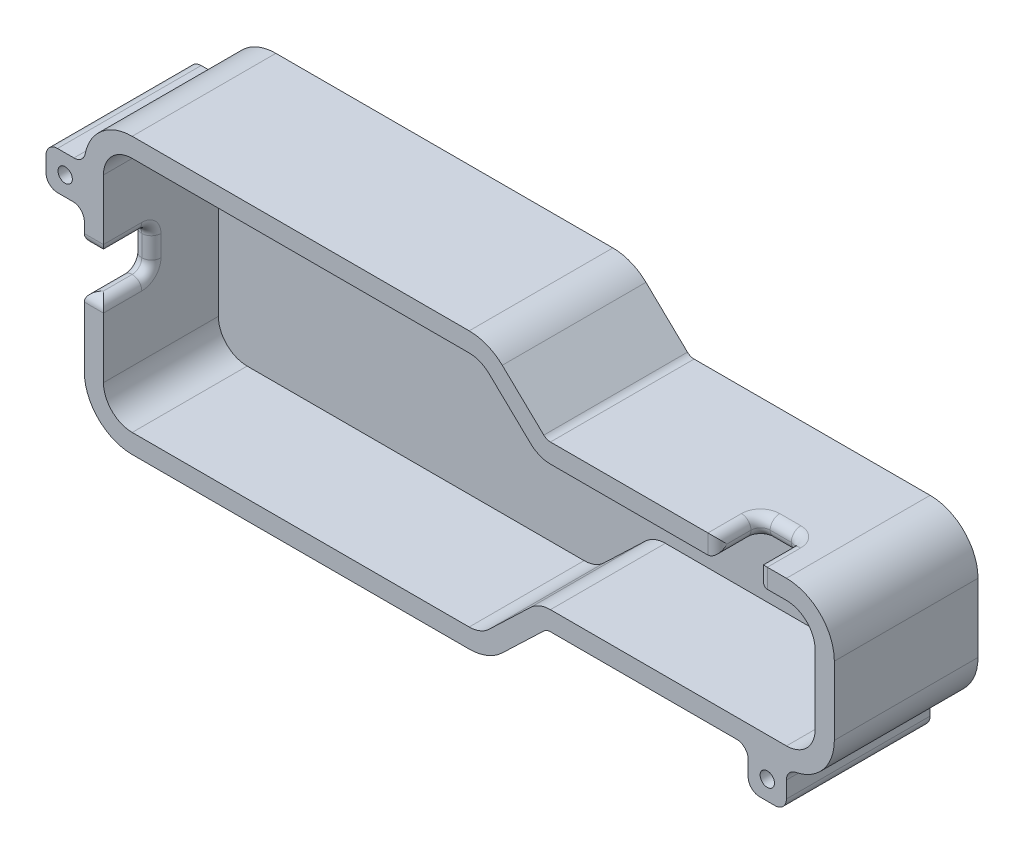
SolidWorks part; units mm, degrees
ref_plane "Front Plane" through (0, 0, 0) normal (0, 0, 1) x (1, 0, 0)
ref_plane "Top Plane" through (0, 0, 0) normal (0, 1, 0) x (1, 0, 0)
ref_plane "Right Plane" through (0, 0, 0) normal (1, 0, 0) x (0, 0, -1)
sketch "Sketch2" plane through (0, 0, 0) normal (0, 0, 1) x (1, 0, 0)
  line L0 (-34.29, 10.16) -> (0, 10.16)
  line L1 (-34.29, 10.16) -> (-34.29, 0)
  line L2 (-34.29, 0) -> (0, 0)
  line L3 (0, 10.16) -> (0, 0)
  line L4 (-69.31, 13.97) -> (-36.29, 13.97)
  line L5 (-69.31, 13.97) -> (-69.31, -3.81)
  line L6 (-69.31, -3.81) -> (-36.29, -3.81)
  line L7 (-36.29, 13.97) -> (-36.29, -3.81)
  line L8 (-31.29, 10.16) -> (-31.29, 0)
  line L9 (-71.31, 15.97) -> (-34.29, 15.97)
  line L10 (-34.29, 15.97) -> (-34.29, 12.16)
  line L11 (-34.29, 12.16) -> (-31.29, 12.16)
  line L12 (-31.29, 12.16) -> (-31.29, -2)
  line L13 (-31.29, -2) -> (-34.29, -2)
  line L14 (-34.29, -2) -> (-34.29, -5.81)
  line L15 (-34.29, -5.81) -> (-71.31, -5.81)
  line L16 (-71.31, -5.81) -> (-71.31, 15.97)
  point P4 (-34.29, 5.08)
  point P5 (-36.29, 5.08)
  dimension "D1" = 2
  dimension "D2" = 2
  dimension "D3" = 2
  dimension "D5" = 2
  dimension "D4" = 2
  dimension "D6" = 0
  dimension "pcb_overflow" = 2
  dimension "arduino_length" = 33.02
  dimension "arduino_width" = 17.78
  dimension "imu_header" = 3
  dimension "imu_length" = 34.29
  dimension "imu_width" = 10.16
sketch "Sketch3" plane through (0, 0, 0) normal (0, 0, 1) x (1, 0, 0)
  line L0 (-69.81, 17.47) -> (-34.6251, 17.47)
  line L1 (-32.5518, 16.6383) -> (-28.2152, 12.4917)
  line L2 (-26.1419, 11.66) -> (-1.5, 11.66)
  line L3 (1.5, 8.66) -> (1.5, 1.5)
  line L4 (-1.5, -1.5) -> (-26.1419, -1.5)
  line L5 (-28.2152, -2.3317) -> (-32.5518, -6.4783)
  line L6 (-34.6251, -7.31) -> (-69.81, -7.31)
  line L7 (-72.81, -4.31) -> (-72.81, 14.47)
  line L8 (-71.31, 15.97) -> (-34.29, 15.97) construction
  line L9 (-34.29, -5.81) -> (-71.31, -5.81) construction
  line L11 (-34.29, 0) -> (0, 0) construction
  line L12 (0, 10.16) -> (0, 0) construction
  line L13 (-71.31, -5.81) -> (-71.31, 15.97) construction
  line L14 (-69.81, 19.47) -> (-34.6251, 19.47)
  line L15 (-31.1696, 18.0838) -> (-26.833, 13.9372)
  line L16 (-26.1419, 13.66) -> (-1.5, 13.66)
  line L17 (3.5, 8.66) -> (3.5, 1.5)
  line L18 (-1.5, -3.5) -> (-26.1419, -3.5)
  line L19 (-26.833, -3.7772) -> (-31.1696, -7.9238)
  line L20 (-34.6251, -9.31) -> (-69.81, -9.31)
  line L21 (-74.81, -4.31) -> (-74.81, 14.47)
  arc A0 (-69.81, -7.31) -> (-72.81, -4.31) centre (-69.81, -4.31) cw
  arc A1 (-1.5, 11.66) -> (1.5, 8.66) centre (-1.5, 8.66) cw
  arc A2 (1.5, 1.5) -> (-1.5, -1.5) centre (-1.5, 1.5) cw
  arc A3 (-32.5518, -6.4783) -> (-34.6251, -7.31) centre (-34.6251, -4.31) cw
  arc A4 (-26.1419, -1.5) -> (-28.2152, -2.3317) centre (-26.1419, -4.5) ccw
  arc A5 (-28.2152, 12.4917) -> (-26.1419, 11.66) centre (-26.1419, 14.66) ccw
  arc A6 (-34.6251, 17.47) -> (-32.5518, 16.6383) centre (-34.6251, 14.47) cw
  arc A7 (-69.81, 17.47) -> (-72.81, 14.47) centre (-69.81, 14.47) ccw
  arc A8 (-34.6251, 19.47) -> (-31.1696, 18.0838) centre (-34.6251, 14.47) cw
  arc A9 (-26.833, 13.9372) -> (-26.1419, 13.66) centre (-26.1419, 14.66) ccw
  arc A10 (-1.5, 13.66) -> (3.5, 8.66) centre (-1.5, 8.66) cw
  arc A11 (3.5, 1.5) -> (-1.5, -3.5) centre (-1.5, 1.5) cw
  arc A12 (-26.1419, -3.5) -> (-26.833, -3.7772) centre (-26.1419, -4.5) ccw
  arc A13 (-31.1696, -7.9238) -> (-34.6251, -9.31) centre (-34.6251, -4.31) cw
  arc A14 (-69.81, -9.31) -> (-74.81, -4.31) centre (-69.81, -4.31) cw
  arc A15 (-69.81, 19.47) -> (-74.81, 14.47) centre (-69.81, 14.47) ccw
  point P26 (-33.4216, -7.31)
  point P29 (-27.3454, -1.5)
  point P32 (-27.3454, 11.66)
  point P35 (-33.4216, 17.47)
  dimension "D5" = 3
  dimension "D1" = 1.5
  dimension "D2" = 1.5
  dimension "D3" = 1.5
  dimension "D4" = 1.5
  dimension "gap_from_case" = 1.5
  dimension "case_slope_length" = 6
  dimension "case_thickness" = 2
extrude "Boss-Extrude2" add sketch "Sketch3" along normal blind 12 and the other way blind 3
sketch "Sketch5" plane through (0, 0, -3) normal (0, 0, -1) x (-1, 0, 0)
  line L0 (-1.5, 1.5) -> (-1.5, 8.66) construction
  line L1 (26.1419, -1.5) -> (1.5, -1.5) construction
  line L2 (32.5518, -6.4783) -> (28.2152, -2.3317) construction
  line L3 (69.81, -7.31) -> (34.6251, -7.31) construction
  line L4 (72.81, 14.47) -> (72.81, -4.31) construction
  line L5 (-1.5, 1.5) -> (-1.5, 8.66)
  line L6 (26.1419, -1.5) -> (1.5, -1.5)
  line L7 (32.5518, -6.4783) -> (28.2152, -2.3317)
  line L8 (72.81, -4.31) -> (72.81, 14.47)
  line L9 (34.6251, -7.31) -> (69.81, -7.31)
  line L10 (28.2152, -2.3317) -> (32.5518, -6.4783)
  line L11 (1.5, -1.5) -> (26.1419, -1.5)
  line L12 (-1.5, 8.66) -> (-1.5, 1.5)
  line L13 (26.1419, 11.66) -> (1.5, 11.66)
  line L14 (32.5518, 16.6383) -> (28.2152, 12.4917)
  line L15 (69.81, 17.47) -> (34.6251, 17.47)
  line L16 (72.81, -4.31) -> (72.81, 14.47)
  line L17 (34.6251, -7.31) -> (69.81, -7.31)
  line L18 (28.2152, -2.3317) -> (32.5518, -6.4783)
  line L19 (1.5, -1.5) -> (26.1419, -1.5)
  line L20 (-1.5, 8.66) -> (-1.5, 1.5)
  line L21 (26.1419, 11.66) -> (1.5, 11.66)
  line L22 (32.5518, 16.6383) -> (28.2152, 12.4917)
  line L23 (69.81, 17.47) -> (34.6251, 17.47)
  line L24 (69.81, -7.31) -> (34.6251, -7.31)
  line L25 (72.81, 14.47) -> (72.81, -4.31)
  arc A0 (1.5, 11.66) -> (-1.5, 8.66) centre (1.5, 8.66) ccw construction
  arc A1 (-1.5, 1.5) -> (1.5, -1.5) centre (1.5, 1.5) ccw construction
  arc A2 (28.2152, -2.3317) -> (26.1419, -1.5) centre (26.1419, -4.5) ccw construction
  arc A3 (32.5518, -6.4783) -> (34.6251, -7.31) centre (34.6251, -4.31) ccw construction
  arc A4 (69.81, -7.31) -> (72.81, -4.31) centre (69.81, -4.31) ccw construction
  arc A5 (72.81, 14.47) -> (69.81, 17.47) centre (69.81, 14.47) ccw construction
  arc A6 (1.5, 11.66) -> (-1.5, 8.66) centre (1.5, 8.66) ccw
  arc A7 (-1.5, 1.5) -> (1.5, -1.5) centre (1.5, 1.5) ccw
  arc A8 (69.81, -7.31) -> (72.81, -4.31) centre (69.81, -4.31) ccw
  arc A9 (32.5518, -6.4783) -> (34.6251, -7.31) centre (34.6251, -4.31) ccw
  arc A10 (28.2152, -2.3317) -> (26.1419, -1.5) centre (26.1419, -4.5) ccw
  arc A11 (-1.5, 1.5) -> (1.5, -1.5) centre (1.5, 1.5) ccw
  arc A12 (1.5, 11.66) -> (-1.5, 8.66) centre (1.5, 8.66) ccw
  arc A13 (26.1419, 11.66) -> (28.2152, 12.4917) centre (26.1419, 14.66) ccw
  arc A14 (34.6251, 17.47) -> (32.5518, 16.6383) centre (34.6251, 14.47) ccw
  arc A15 (72.81, 14.47) -> (69.81, 17.47) centre (69.81, 14.47) ccw
  arc A16 (69.81, -7.31) -> (72.81, -4.31) centre (69.81, -4.31) ccw
  arc A17 (32.5518, -6.4783) -> (34.6251, -7.31) centre (34.6251, -4.31) ccw
  arc A18 (28.2152, -2.3317) -> (26.1419, -1.5) centre (26.1419, -4.5) ccw
  arc A19 (-1.5, 1.5) -> (1.5, -1.5) centre (1.5, 1.5) ccw
  arc A20 (1.5, 11.66) -> (-1.5, 8.66) centre (1.5, 8.66) ccw
  arc A21 (26.1419, 11.66) -> (28.2152, 12.4917) centre (26.1419, 14.66) ccw
  arc A22 (34.6251, 17.47) -> (32.5518, 16.6383) centre (34.6251, 14.47) ccw
  arc A23 (72.81, 14.47) -> (69.81, 17.47) centre (69.81, 14.47) ccw
  arc A24 (28.2152, -2.3317) -> (26.1419, -1.5) centre (26.1419, -4.5) ccw
  arc A25 (32.5518, -6.4783) -> (34.6251, -7.31) centre (34.6251, -4.31) ccw
  arc A26 (69.81, -7.31) -> (72.81, -4.31) centre (69.81, -4.31) ccw
  arc A27 (72.81, 14.47) -> (69.81, 17.47) centre (69.81, 14.47) ccw
  line M17 (72.81, 14.47) -> (72.81, -4.31)
  arc M18 (72.81, -4.31) -> (69.81, -7.31) centre (69.81, -4.31) cw
  line M19 (69.81, -7.31) -> (34.6251, -7.31)
  arc M20 (34.6251, -7.31) -> (32.5518, -6.4783) centre (34.6251, -4.31) cw
  line M21 (32.5518, -6.4783) -> (28.2152, -2.3317)
  arc M22 (28.2152, -2.3317) -> (26.1419, -1.5) centre (26.1419, -4.5) ccw
  line M23 (26.1419, -1.5) -> (1.5, -1.5)
  arc M24 (1.5, -1.5) -> (-1.5, 1.5) centre (1.5, 1.5) cw
  line M25 (-1.5, 1.5) -> (-1.5, 8.66)
  arc M26 (-1.5, 8.66) -> (1.5, 11.66) centre (1.5, 8.66) cw
  line M27 (1.5, 11.66) -> (26.1419, 11.66)
  arc M28 (26.1419, 11.66) -> (28.2152, 12.4917) centre (26.1419, 14.66) ccw
  line M29 (28.2152, 12.4917) -> (32.5518, 16.6383)
  arc M30 (32.5518, 16.6383) -> (34.6251, 17.47) centre (34.6251, 14.47) cw
  line M31 (34.6251, 17.47) -> (69.81, 17.47)
  arc M32 (69.81, 17.47) -> (72.81, 14.47) centre (69.81, 14.47) cw
  dimension "D1" = 0
extrude "Boss-Extrude3" add sketch "Sketch5" against normal blind 3 contours M17 M32 M31 M30 M29 M28 M27 M26 M25 M24 M23 M22 M21 M20 M19 M18 region at (-41.0126, 5.08, -3)
sketch "Sketch6" plane through (-74.81, 0, 0) normal (-1, 0, 0) x (0, 0, 1)
  line L0 (12, 5.08) -> (7, 5.08)
  line L1 (12, 14.47) -> (12, -4.31) construction
  line L2 (7, 7.18) -> (7, 5.08)
  line L3 (7, 7.18) -> (12, 7.18)
  line L4 (7, 5.08) -> (7, 2.98)
  line L5 (7, 2.98) -> (12, 2.98)
  line M2 (12, -4.31) -> (12, 14.47)
  dimension "D1" = 5
  dimension "D2" = 2.1
extrude "Cut-Extrude1" cut sketch "Sketch6" against normal blind 10 contours L3 L2 L0 M2 | L4 L5 L0 M2 region at (-74.81, 4.03, 9.5) region at (-74.81, 6.13, 9.5)
sketch "Sketch7" plane through (0, 13.66, 0) normal (0, 1, 0) x (1, 0, 0)
  line L0 (-4.5, -12) -> (-4.5, -7.5)
  line L1 (-1.5, -12) -> (-26.1419, -12) construction
  line L2 (-4.5, -7.5) -> (-8.7, -7.5)
  line L3 (-8.7, -7.5) -> (-8.7, -12)
  line L5 (-1.5, 3) -> (-1.5, -12) construction
  line L6 (-4.5, -12) -> (-8.7, -12)
  dimension "D1" = 4.2
  dimension "D2" = 4.5
  dimension "D3" = 3
extrude "Cut-Extrude2" cut sketch "Sketch7" against normal blind 10
fillet "Fillet1" radius 1 20 edges at (-4.5, 11.66, 9.75) (-4.5, 13.66, 9.75) (-8.7, 12.66, 7.5) (-8.7, 11.66, 9.75) (-4.5, 12.66, 12) (-6.6, 11.66, 7.5) (-4.5, 12.66, 7.5) (-6.6, 13.66, 7.5) (-8.7, 13.66, 9.75) (-8.7, 12.66, 12) (-73.81, 2.98, 7) (-73.81, 7.18, 7) (-72.81, 7.18, 9.5) (-72.81, 5.08, 7) (-72.81, 2.98, 9.5) (-73.81, 2.98, 12) (-74.81, 2.98, 9.5) (-74.81, 7.18, 9.5) (-74.81, 5.08, 7) (-73.81, 7.18, 12)
sketch "Sketch8" plane through (0, 0, 12) normal (0, 0, 1) x (1, 0, 0)
  line L1 (-74.81, 14.47) -> (-78.81, 14.47)
  line L2 (-74.81, 14.47) -> (-74.81, 10.47)
  line L3 (-74.81, 10.47) -> (-78.81, 10.47)
  line L4 (-78.81, 14.47) -> (-78.81, 10.47)
  line L5 (-1.5, -3.5) -> (-5.5, -3.5)
  line L6 (-1.5, -3.5) -> (-1.5, -7.5)
  line L7 (-1.5, -7.5) -> (-5.5, -7.5)
  line L8 (-5.5, -3.5) -> (-5.5, -7.5)
  dimension "D1" = 4
extrude "Boss-Extrude4" add sketch "Sketch8" against normal through all
fillet "Fillet2" radius 1.2 8 edges at (-1.5, -3.5, 4.5) (-1.5, -7.5, 4.5) (-5.5, -7.5, 4.5) (-5.5, -3.5, 4.5) (-74.81, 14.47, 4.5) (-74.81, 10.47, 4.5) (-78.81, 14.47, 4.5) (-78.81, 10.47, 4.5)
sketch "Sketch9" plane through (0, 0, 12) normal (0, 0, 1) x (1, 0, 0)
  line L0 (-75.8928, 14.47) -> (-77.61, 14.47) construction
  line L1 (-78.81, 13.27) -> (-78.81, 11.67) construction
  line L2 (-4.3, -7.5) -> (-2.7, -7.5) construction
  line L3 (-5.5, -4.7) -> (-5.5, -6.3) construction
  circle A0 centre (-76.81, 12.47) radius 0.75
  circle A1 centre (-3.5, -5.5) radius 0.75
  dimension "D5" = 1.5
  dimension "D6" = 1.5
  dimension "D1" = 2
  dimension "D2" = 2
  dimension "D3" = 2
  dimension "D4" = 2
extrude "Cut-Extrude3" cut sketch "Sketch9" against normal through all
sketch "Sketch10" plane through (0, 0, -3) normal (0, 0, -1) x (-1, 0, 0)
  line L0 (34.6251, 19.47) -> (69.81, 19.47) construction
  line L1 (74.81, 9.27) -> (74.81, -4.31) construction
  circle A0 centre (62.81, 5.08) radius 3.5
  dimension "D3" = 7
  dimension "D1" = 14.39
  dimension "D2" = 12
extrude "Cut-Extrude4" cut sketch "Sketch10" against normal blind 1.5
fillet "Fillet3" radius 0.3 1 edges at (-66.31, 5.08, -3)
equation "\"D5@Sketch2\"=\"pcb_overflow\""
equation "\"D1@Sketch2\"=\"pcb_overflow\""
equation "\"D2@Sketch2\"=\"pcb_overflow\""
equation "\"D4@Sketch2\"=\"pcb_overflow\""
equation "\"D3@Sketch2\"=\"pcb_overflow\""
equation "\"D1@Sketch3\"=\"gap_from_case\""
equation "\"D2@Sketch3\"=\"gap_from_case\""
equation "\"D3@Sketch3\"=\"gap_from_case\""
equation "\"D4@Sketch3\"=\"gap_from_case\""
